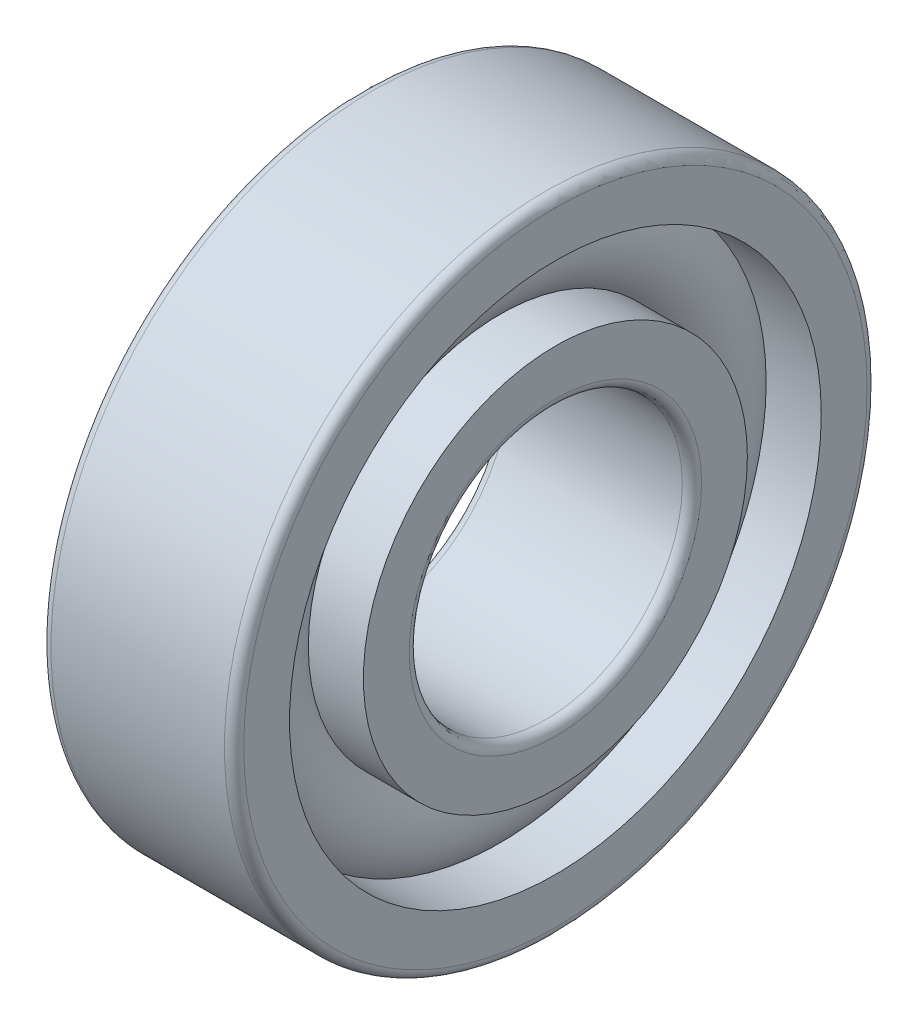
SolidWorks part; units mm, degrees
ref_plane "Plane1" through (0, 0, 0) normal (0, 0, 1) x (1, 0, 0)
ref_plane "Plane2" through (0, 0, 0) normal (0, 1, 0) x (1, 0, 0)
ref_plane "Plane3" through (0, 0, 0) normal (1, 0, 0) x (0, 0, -1)
sketch "Clipboard" plane through (0, 0, 0) normal (0, 0, 1) x (1, 0, 0)
  line L0 (-10, 0) -> (10, 0) construction
  line L1 (0, 0) -> (22.3471, -0.7804)
  line L2 (0, 0) -> (14.2413, 0.4973)
  line L3 (0, 0) -> (22.3471, -0.7804)
  line L4 (0, 0) -> (-22.3573, -0.3902)
  dimension "BallCLRad" = 14.25
sketch "CagSpiSke" plane through (0, 0, 0) normal (0, 0, 1) x (1, 0, 0)
  line L0 (0.345, 13.675) -> (0.345, 14.825)
  line L1 (0.345, 14.825) -> (-0.345, 14.825)
  line L2 (-0.345, 14.825) -> (-0.345, 13.675)
  line L3 (-0.345, 13.675) -> (0.345, 13.675)
  line L4 (-20.6375, 0) -> (20.6375, 0) construction
  line L5 (0, 0) -> (0, 23.7692) construction
  dimension "OD" = 29.65
  dimension "ID" = 27.35
revolve "CageSpine" add sketch "CagSpiSke" angle 0.001 about L4 reverse direction yes
ref_axis "Axis1" through (-50, 0, 0) along (1, 0, 0)
sketch "CagBalSke" plane through (0, 0, 0) normal (0, 0, 1) x (1, 0, 0)
  line L0 (-3.795, 14.25) -> (3.795, 14.25)
  line L1 (-1.905, 14.25) -> (1.905, 14.25) construction
  line L2 (-10, 0) -> (10, 0) construction
  line L3 (0, 0) -> (0, 24) construction
  arc A0 (3.795, 14.25) -> (-3.795, 14.25) centre (0, 14.25) cw
  dimension "BallCLRad" = 14.25
revolve "CageBall" [suppressed] add sketch "CagBalSke" angle 360 about L1 reverse direction yes
pattern_circular "CageBalls" [suppressed] count 2 every 180 about axis through (-50, 0, 0) along (1, 0, 0)
sketch "CagTrmODSke" plane through (0, 0, 0) normal (0, 0, 1) x (1, 0, 0)
  line L0 (3.796, 14.825) -> (3.796, 18.046)
  line L1 (3.796, 18.046) -> (-3.796, 18.046)
  line L2 (-3.796, 18.046) -> (-3.796, 14.825)
  line L3 (-3.796, 14.825) -> (3.796, 14.825)
  line L4 (-20.6375, 0) -> (20.6375, 0) construction
  line L5 (0, 0) -> (0, 25) construction
  dimension "Width" = 7.592
  dimension "ID" = 29.65
  dimension "OD" = 36.092
revolve "CageTrimOD" [suppressed] cut sketch "CagTrmODSke" angle 360 about L4 reverse direction yes
sketch "CagTrmIDSke" plane through (0, 0, 0) normal (0, 0, 1) x (1, 0, 0)
  line L0 (3.796, 10.456) -> (3.796, 13.675)
  line L1 (3.796, 13.675) -> (-3.796, 13.675)
  line L2 (-3.796, 13.675) -> (-3.796, 10.456)
  line L3 (-3.796, 10.456) -> (3.796, 10.456)
  line L4 (-20.6375, 0) -> (20.6375, 0) construction
  line L5 (0, 0) -> (0, 25) construction
  dimension "Width" = 7.592
  dimension "ID" = 20.912
  dimension "OD" = 27.35
revolve "CageTrimID" [suppressed] cut sketch "CagTrmIDSke" angle 360 about L4 reverse direction yes
sketch "BalSimSke" plane through (0, 0, 0) normal (0, 0, 1) x (1, 0, 0)
  line L0 (-10, 0) -> (10, 0) construction
  line L1 (-10, 14.25) -> (10, 14.25) construction
  line L2 (0, 0) -> (0, 23) construction
  circle A0 centre (0, 14.25) radius 3.45
  dimension "BallCLRad" = 14.25
  dimension "Ball_diameter" = 6.9
revolve "BallsSimplified" add sketch "BalSimSke" angle 360 about L0
sketch "BalDetSke" plane through (0, 0, 0) normal (0, 0, 1) x (1, 0, 0)
  line L0 (-3.45, 14.25) -> (3.45, 14.25)
  line L1 (-1.905, 14.25) -> (1.905, 14.25) construction
  line L2 (0, 0) -> (0, 25) construction
  arc A0 (3.45, 14.25) -> (-3.45, 14.25) centre (0, 14.25) cw
  dimension "BallCLRad" = 14.25
  dimension "Ball_diameter" = 6.9
revolve "BallDetailed" [suppressed] add sketch "BalDetSke" angle 360 about L1 reverse direction yes
sketch "InnRacSke" plane through (0, 0, 0) normal (0, 0, 1) x (1, 0, 0)
  line L0 (-2.5378, 11.95) -> (-6, 11.95)
  line L1 (-6, 11.95) -> (-6, 9.1)
  line L2 (-5.4, 8.5) -> (5.4, 8.5)
  line L3 (6, 9.1) -> (6, 11.95)
  line L4 (6, 11.95) -> (2.5378, 11.95)
  line L5 (-20.6375, 0) -> (20.6375, 0) construction
  line L6 (0, 0) -> (0, 30) construction
  arc A0 (-6, 9.1) -> (-5.4, 8.5) centre (-5.4, 9.1) ccw
  arc A1 (5.4, 8.5) -> (6, 9.1) centre (5.4, 9.1) ccw
  arc A2 (2.5378, 11.95) -> (-2.5378, 11.95) centre (0, 14.25) cw
  dimension "BallCLRad" = 14.25
  dimension "Fillet_radius" = 0.6
  dimension "Ball_diameter" = 6.85
  dimension "ID" = 17
  dimension "OD" = 23.9
  dimension "Width" = 12
revolve "InnerRace" add sketch "InnRacSke" angle 360 about L5 reverse direction yes
sketch "OutRacSke" plane through (0, 0, 0) normal (0, 0, 1) x (1, 0, 0)
  line L0 (-2.5378, 16.55) -> (-6, 16.55)
  line L1 (-6, 16.55) -> (-6, 19.4)
  line L2 (-5.4, 20) -> (5.4, 20)
  line L3 (6, 19.4) -> (6, 16.55)
  line L4 (6, 16.55) -> (2.5378, 16.55)
  line L5 (-20.6375, 0) -> (20.6375, 0) construction
  line L6 (0, 0) -> (0, 30) construction
  arc A0 (-6, 19.4) -> (-5.4, 20) centre (-5.4, 19.4) cw
  arc A1 (5.4, 20) -> (6, 19.4) centre (5.4, 19.4) cw
  arc A2 (2.5378, 16.55) -> (-2.5378, 16.55) centre (0, 14.25) ccw
  dimension "BallCLRad" = 14.25
  dimension "Fillet_radius" = 0.6
  dimension "Ball_diameter" = 6.85
  dimension "Width" = 12
revolve "OuterRace" add sketch "OutRacSke" angle 360 about L5 reverse direction yes
pattern_circular "BallsDetailed" [suppressed] count 2 every 180 about axis through (-50, 0, 0) along (1, 0, 0)
equation "\"BallCLRad@Clipboard\" = ( \"OD@OutRacSke\" + \"ID@InnRacSke\" ) / 4"
equation "\"BallCLRad@BalSimSke\" = \"BallCLRad@Clipboard\""
equation "\"BallCLRad@BalDetSke\" = \"BallCLRad@Clipboard\""
equation "\"BallCLRad@InnRacSke\" = \"BallCLRad@Clipboard\""
equation "\"BallCLRad@OutRacSke\" = \"BallCLRad@Clipboard\""
equation "\"Ball_diameter@InnRacSke\" = \"Ball_diameter@BalDetSke\" - 0.05"
equation "\"Ball_diameter@OutRacSke\" = \"Ball_diameter@BalDetSke\" - 0.05"
equation "\"Ball_diameter@BalSimSke\" = \"Ball_diameter@BalDetSke\""
equation "\"Width@OutRacSke\" = \"Width@InnRacSke\""
equation "\"Fillet_radius@OutRacSke\" = \"Fillet_radius@InnRacSke\""
equation "\"Max_count@Clipboard\" = int( 3.14159265 / atn(( \"Ball_diameter@BalDetSke\" / 2) / sqr( \"BallCLRad@Clipboard\"  *  \"BallCLRad@Clipboard\" - ( \"Ball_diameter@BalDetSke\" / 2) *  ( \"Ball_diameter@BalDetSke\" / 2))))"
equation "\"Max_count@Clipboard\" = ((sgn( \"Max_count@Clipboard\" - \"Count@Clipboard\" )-1)*( \"Max_count@Clipboard\" - \"Count@Clipboard\" ))/-2+ \"Count@Clipboard\""
equation "\"Count@BallsDetailed\" = int( \"Show_count@Clipboard\" ) "
equation "\"Count@BallsDetailed\" = ((sgn( \"Count@BallsDetailed\" - \"Max_count@Clipboard\" )-1)*( \"Count@BallsDetailed\" - \"Max_count@Clipboard\" ))/-2+ \"Max_count@Clipboard\""
equation "\"Count@BallsDetailed\" = ((sgn( \"Count@BallsDetailed\" - \"Min_count@Clipboard\" )+1)*( \"Count@BallsDetailed\" - \"Min_count@Clipboard\"))/2 +\"Min_count@Clipboard\""
equation "\"Angle@BallsDetailed\" = 360.0 / \"Max_count@Clipboard\""
equation "\"BallCLRad@CagBalSke\" = \"BallCLRad@Clipboard\""
equation "\"Count@CageBalls\" = \"Count@BallsDetailed\""
equation "\"Angle@CageBalls\" = \"Angle@BallsDetailed\""
equation "\"Angle@CageSpine\" =  \"Angle@CageBalls\" * ( \"Count@CageBalls\" -1 + int( \"Count@CageBalls\" / \"Max_count@Clipboard\" ) )  + 0.001 -  int( \"Count@CageBalls\" / \"Max_count@Clipboard\" ) * 0.001"
equation "\"Angle@CageSpine\" =  \"Angle@CageSpine\" * int( \"Min_count@Clipboard\" / 2) + int(1 / \"Min_count@Clipboard\")  * 0.001"
equation "\"CageWallOD@CagBalSke\" =  \"Ball_diameter@BalDetSke\" * 1.1"
equation "\"Thickness@CagSpiSke\" =  \"Ball_diameter@BalDetSke\" * 0.1"
equation "\"OD@CagTrmODSke\" = \"BallCLRad@Clipboard\" * 2 + \"CageWallOD@CagBalSke\" + 0.002"
equation "\"ID@CagTrmODSke\" = \"BallCLRad@Clipboard\" * 2 + \"Ball_diameter@BalDetSke\" / 6"
equation "\"OD@CagTrmIDSke\" = \"BallCLRad@Clipboard\" * 2 - \"Ball_diameter@BalDetSke\" / 6"
equation "\"ID@CagTrmIDSke\" = \"BallCLRad@Clipboard\" * 2 - \"CageWallOD@CagBalSke\" + 0.002"
equation "\"OD@CagSpiSke\" = \"ID@CagTrmODSke\""
equation "\"ID@CagSpiSke\" = \"OD@CagTrmIDSke\""
equation "\"Width@CagTrmODSke\" = \"CageWallOD@CagBalSke\" + 0.002"
equation "\"Width@CagTrmIDSke\" = \"CageWallOD@CagBalSke\" + 0.002"
